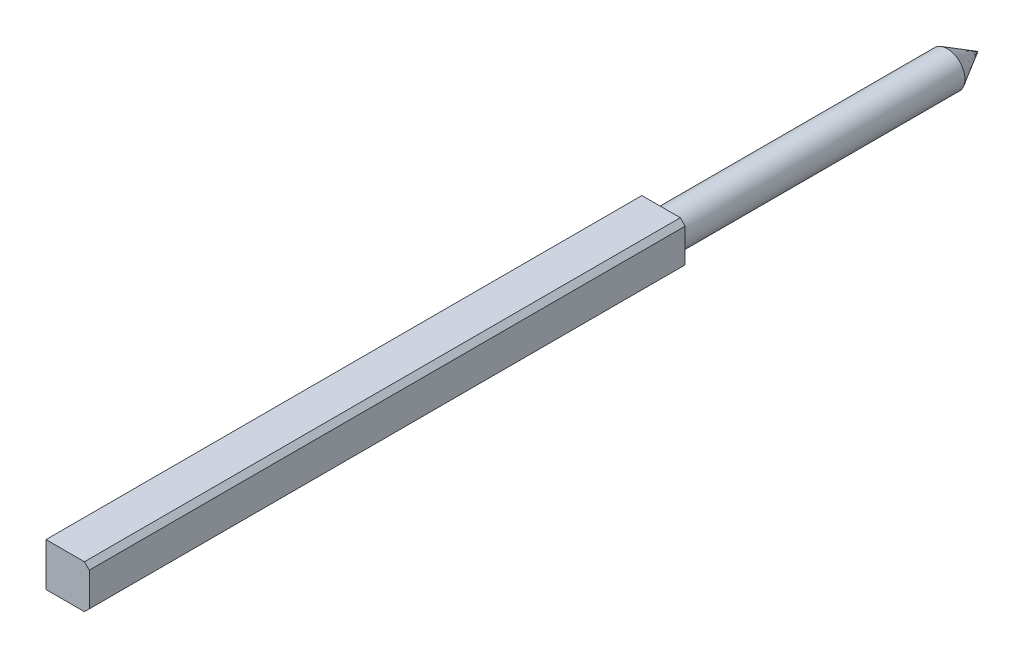
SolidWorks part; units mm, degrees
ref_plane "Front Plane" through (0, 0, 0) normal (0, 0, 1) x (1, 0, 0)
ref_plane "Top Plane" through (0, 0, 0) normal (0, 1, 0) x (1, 0, 0)
ref_plane "Right Plane" through (0, 0, 0) normal (1, 0, 0) x (0, 0, -1)
sketch "Sketch1" plane through (0, 0, 0) normal (0, 0, 1) x (1, 0, 0)
  line L1 (-3.05, -3.05) -> (3.05, -3.05)
  line L2 (-3.05, -3.05) -> (-3.05, 3.05)
  line L3 (-3.05, 3.05) -> (3.05, 3.05)
  line L4 (3.05, -3.05) -> (3.05, 3.05)
  line L5 (-3.05, -3.05) -> (3.05, 3.05) construction
  line L6 (-3.05, 3.05) -> (3.05, -3.05) construction
  circle A0 centre (0, 0) radius 2.5
  point P0 (0, 0)
  dimension "D3" = 5
  dimension "D1" = 6.1
  dimension "D2" = 6.1
extrude "Boss-Extrude1" add sketch "Sketch1" along normal blind 84 contours L2 L3 L4 L1
extrude "Boss-Extrude2" add sketch "Sketch1<4>" against normal blind 40 contours A0
sketch "Sketch1<4>" plane through (0, 0, 0) normal (0, 0, 1) x (1, 0, 0) same geometry as "Sketch1"
sketch "Sketch6" plane through (0, 0, -40) normal (0, 0, -1) x (-1, 0, 0)
  circle A0 centre (0, 0) radius 2.5 construction
  circle A1 centre (0, 0) radius 2.5
extrude "Boss-Extrude3" add sketch "Sketch6" along normal blind 40 draft 30
chamfer "chamfer_lock" [suppressed] distance 0.889 angle 45
chamfer "chamfer_base" distance 0.686 angle 45 2 edges at (3.05, -3.05, 42) (3.05, 3.05, 42)
chamfer "chamfer_lock_right" [suppressed] distance 0.889 angle 45
